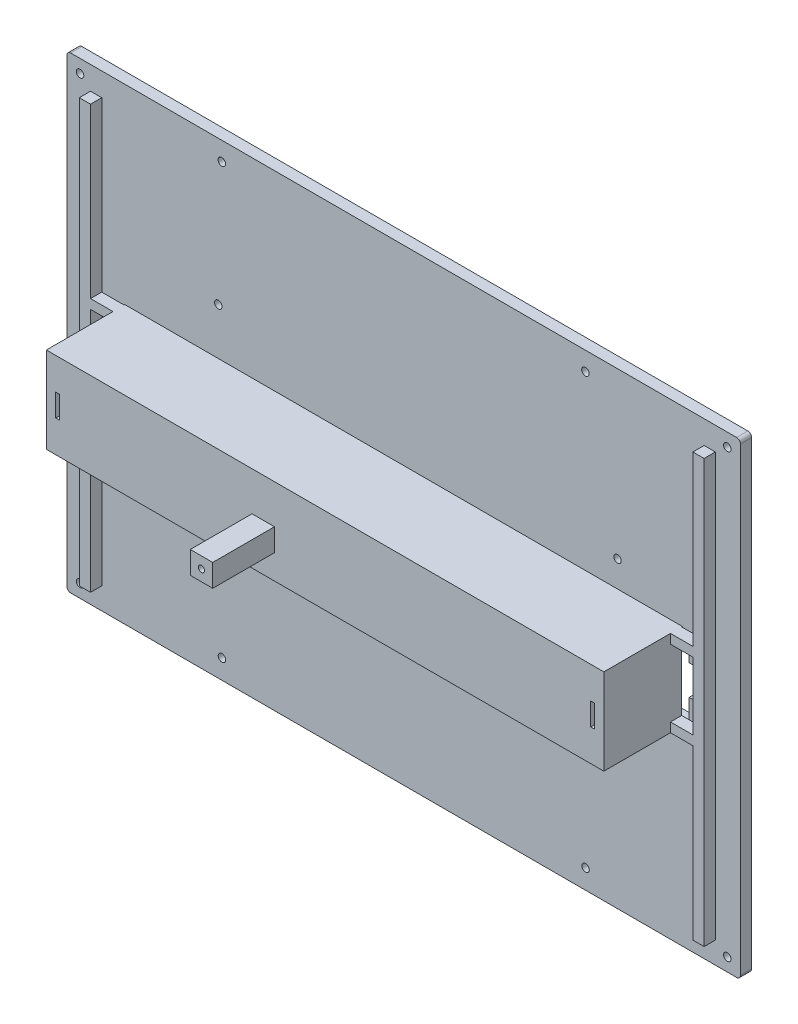
SolidWorks part; units mm, degrees
ref_plane "前视基准面" through (0, 0, 0) normal (0, 0, 1) x (1, 0, 0)
ref_plane "上视基准面" through (0, 0, 0) normal (0, 1, 0) x (1, 0, 0)
ref_plane "右视基准面" through (0, 0, 0) normal (1, 0, 0) x (0, 0, -1)
sketch "草图1" plane through (0, 0, 0) normal (0, 0, 1) x (1, 0, 0)
  line L1 (-90, 62.5) -> (90, 62.5)
  line L2 (-90, 62.5) -> (-90, -62.5)
  line L3 (-90, -62.5) -> (90, -62.5)
  line L4 (90, 62.5) -> (90, -62.5)
  line L5 (-90, 62.5) -> (90, -62.5) construction
  line L6 (-90, -62.5) -> (90, 62.5) construction
  point P0 (0, 0)
  dimension "D1" = 125
  dimension "D2" = 180
extrude "凸台-拉伸1" add sketch "草图1" along normal blind 3
sketch "草图7" plane through (0, 0, 0) normal (0, 0, -1) x (-1, 0, 0)
  line L1 (-72, 10.5) -> (72, 10.5)
  line L2 (-72, 10.5) -> (-72, -10.5)
  line L3 (-72, -10.5) -> (72, -10.5)
  line L4 (72, 10.5) -> (72, -10.5)
  line L5 (0, 0) -> (72.729, 0) construction
  line L8 (0, 0) -> (0, -50.9103) construction
  dimension "D1" = 21
  dimension "D2" = 144
extrude "电池位切除-拉伸3" cut sketch "草图7" against normal up to next
sketch "草图8" plane through (0, 0, 3) normal (0, 0, 1) x (1, 0, 0)
  line L0 (-72, 9.5) -> (72, 9.5)
  line L9 (-72, -9.5) -> (72, -9.5)
  line L10 (72, 0) -> (58.7112, 0) construction
  line L12 (72, 10.5) -> (72, -10.5) construction
  line L13 (-74.5, 11.5) -> (74.5, 11.5)
  line L14 (-74.5, 11.5) -> (-74.5, -11.5)
  line L15 (-74.5, -11.5) -> (74.5, -11.5)
  line L16 (74.5, 11.5) -> (74.5, -11.5)
  line L17 (-72, -10.5) -> (-72, 10.5) construction
  line L18 (-72, 10.5) -> (72, 10.5) construction
  line L19 (-72, 10.5) -> (72, 10.5) construction
  line L22 (72, 9.5) -> (72, -9.5)
  line L23 (-72, -10.5) -> (-72, 10.5) construction
  line L24 (-72, -9.5) -> (-72, 9.5)
  dimension "D1" = 2.5
  dimension "D2" = 2.5
  dimension "D3" = 2
  dimension "D4" = 2
extrude "凸台-拉伸2" add sketch "草图8" along normal blind 21
sketch "草图9" plane through (0, 0, 24) normal (0, 0, 1) x (1, 0, 0)
  line L0 (74.5, 11.5) -> (-74.5, 11.5) construction
  line L5 (74.5, 11.5) -> (-74.5, 11.5)
  line L6 (-74.5, -11.5) -> (74.5, -11.5) construction
  line L7 (-74.5, -11.5) -> (74.5, -11.5)
  line L8 (74.5, -11.5) -> (74.5, 11.5) construction
  line L9 (74.5, -11.5) -> (74.5, 11.5)
  line L10 (-74.5, 11.5) -> (-74.5, -11.5) construction
  line L11 (-74.5, 11.5) -> (-74.5, -11.5)
extrude "凸台-拉伸3" add sketch "草图9" against normal blind 2
sketch "草图4" plane through (0, 0, 0) normal (0, 0, -1) x (-1, 0, 0)
  line L0 (72, -10.5) -> (72, 10.5) construction
  line L5 (72, 0) -> (84.6307, 0) construction
  line L10 (83.2374, -53.4277) -> (79.3374, -53.4277) construction
  line L11 (83.2374, -49.6277) -> (83.2374, -53.4277) construction
  line L12 (79.3374, -49.6277) -> (83.2374, -49.6277) construction
  line L29 (72, -4) -> (74.5, -4)
  line L30 (74.5, -4) -> (74.5, 4)
  line L31 (74.5, 4) -> (72, 4)
  line L32 (72, 4) -> (72, -4)
  dimension "D1" = 8
  dimension "D2" = 2.5
extrude "切除-拉伸2" cut sketch "草图4" against normal blind 2 from offset 1.5 offset against normal yes
sketch "草图10" plane through (0, 0, 24) normal (0, 0, 1) x (1, 0, 0)
  line L0 (-16.5366, -1.9347) -> (8.5541, -1.9347) construction
  line L2 (-19.5366, 1.0653) -> (-19.5366, -4.9347)
  line L4 (-13.5366, 1.0653) -> (-13.5366, -4.9347)
  line L5 (-16.5366, -1.9347) -> (-16.5366, 4.0653) construction
  line L6 (0, 0) -> (60.8594, 0) construction
  line L7 (0, 0) -> (0, 60.5) construction
  line L8 (75, 60.5) -> (-75, 60.5) construction
  line L9 (-19.5366, 1.0653) -> (-13.5366, 1.0653)
  line L10 (-19.5366, -4.9347) -> (-13.5366, -4.9347)
  circle A0 centre (-16.5366, -1.9347) radius 0.825
  dimension "D2" = 1.65
  dimension "D1" = 6
extrude "凸台-拉伸4" add sketch "草图10" along normal up to surface (16.5 mm away)
sketch "草图11" plane through (0, 0, 0) normal (0, 0, -1) x (-1, 0, 0)
  circle A0 centre (-48.6147, -57.3) radius 1 construction
  circle A1 centre (-49.55, -23.8) radius 1 construction
  circle A2 centre (57.15, -18.3) radius 1 construction
  circle A3 centre (48.5747, -57.3) radius 1 construction
  circle A4 centre (86.5, 59) radius 1
  circle A5 centre (48.6147, 57.5) radius 1 construction
  circle A6 centre (-57.15, 18.5) radius 1 construction
  circle A7 centre (-48.5747, 57.5) radius 1 construction
  circle A8 centre (-48.6147, -57.3) radius 1
  circle A9 centre (-49.55, -23.8) radius 1
  circle A10 centre (57.15, -18.3) radius 1
  circle A11 centre (48.5747, -57.3) radius 1
  circle A13 centre (48.6147, 57.5) radius 1
  circle A14 centre (-57.15, 18.5) radius 1
  circle A15 centre (-48.5747, 57.5) radius 1
  circle A16 centre (49.55, 24) radius 1 construction
  circle A17 centre (49.55, 24) radius 1
  circle A18 centre (86.5, -59) radius 1
  circle A19 centre (-86.5, -59) radius 1
  circle A20 centre (-86.5, 59) radius 1
  dimension "D1" = 2
  dimension "D2" = 2
  dimension "D3" = 2
  dimension "D4" = 2
extrude "固定螺丝切除-拉伸3" cut sketch "草图11" against normal up to next
sketch "草图12" plane through (0, 0, 0) normal (0, 0, -1) x (-1, 0, 0)
  circle A0 centre (-48.5747, 57.5) radius 2
  circle A1 centre (-57.15, 18.5) radius 2
  circle A2 centre (-49.55, -23.8) radius 2
  circle A3 centre (-48.6147, -57.3) radius 2
  circle A4 centre (48.5747, -57.3) radius 2
  circle A5 centre (57.15, -18.3) radius 2
  circle A7 centre (-86.5, 59) radius 2
  circle A8 centre (48.6147, 57.5) radius 2
  circle A9 centre (49.55, 24) radius 2
  circle A10 centre (-86.5, -59) radius 2
  circle A11 centre (86.5, -59) radius 2
  circle A12 centre (86.5, 59) radius 2
  dimension "D1" = 4
  dimension "D2" = 4
  dimension "D3" = 4
  dimension "D4" = 4
  dimension "D5" = 4
extrude "固定螺丝凹陷切除-拉伸4" cut sketch "草图12" against normal blind 1.2
fillet "圆角1" radius 1 4 edges at (90, -62.5, 1.5) (-90, -62.5, 1.5) (-90, 62.5, 1.5) (90, 62.5, 1.5)
sketch "草图13" plane through (0, 0, 24) normal (0, 0, 1) x (1, 0, 0)
  line L0 (72, 10.5) -> (72, -10.5) construction
  line L1 (72, 3) -> (71, 3)
  line L2 (72, 3) -> (72, -3)
  line L3 (72, -3) -> (71, -3)
  line L4 (71, 3) -> (71, -3)
  line L5 (-72, -10.5) -> (-72, 10.5) construction
  line L6 (-71, 3) -> (-72, 3)
  line L7 (-71, 3) -> (-71, -3)
  line L8 (-71, -3) -> (-72, -3)
  line L9 (-72, 3) -> (-72, -3)
  line L10 (72, 0) -> (59.7453, 0) construction
  dimension "D1" = 1
  dimension "D2" = 6
  dimension "D3" = 1
  dimension "D4" = 6
extrude "切除-拉伸3" cut sketch "草图13" against normal up to next
sketch "草图14" plane through (0, 0, 22) normal (0, 0, -1) x (-1, 0, 0)
  line L0 (72, 10.5) -> (-72, 10.5) construction
  line L1 (-71, 10.5) -> (-69, 10.5)
  line L2 (-71, 10.5) -> (-71, 5.5)
  line L3 (-71, 5.5) -> (-69, 5.5)
  line L4 (-69, 10.5) -> (-69, 5.5)
  line L5 (-72, 0) -> (-60.8543, 0) construction
  line L6 (-72, 10.5) -> (-72, -10.5) construction
  line L7 (72, 0) -> (63.4917, 0) construction
  line L8 (69, 10.5) -> (71, 10.5)
  line L9 (69, 10.5) -> (69, 6)
  line L10 (69, 6) -> (71, 6)
  line L11 (71, 10.5) -> (71, 6)
  line L12 (72, -10.5) -> (72, 10.5) construction
  line L13 (71, -10.5) -> (71, -6)
  line L14 (69, -6) -> (71, -6)
  line L15 (69, -10.5) -> (69, -6)
  line L16 (69, -10.5) -> (71, -10.5)
  line L17 (-69, -10.5) -> (-69, -5.5)
  line L18 (-71, -5.5) -> (-69, -5.5)
  line L19 (-71, -10.5) -> (-71, -5.5)
  line L20 (-71, -10.5) -> (-69, -10.5)
  dimension "D1" = 1
  dimension "D2" = 2
  dimension "D3" = 4.5
  dimension "D4" = 1
  dimension "D5" = 2
  dimension "D6" = 5
extrude "凸台-拉伸5" add sketch "草图14" along normal blind 16
sketch "草图15" plane through (0, 0, 0) normal (0, 0, -1) x (-1, 0, 0)
  line L0 (72, 10.5) -> (-72, 10.5) construction
  line L5 (72, 10.5) -> (72, -10.5)
  line L7 (-72, -10.5) -> (72, -10.5) construction
  line L8 (-76.3, 10.5) -> (72, 10.5)
  line L9 (-76.3, 10.5) -> (-76.3, 4)
  line L10 (-76.3, -10.5) -> (72, -10.5)
  line L12 (-76.3, 4) -> (-79.3365, 4)
  line L14 (-76.3, -4) -> (-79.3365, -4)
  line L15 (-79.3365, 4) -> (-79.3365, -4)
  line L16 (72, 10.5) -> (-72, 10.5) construction
  line L17 (-76.3, -4) -> (-76.3, -10.5)
  line L18 (-76.1, -10.3) -> (-76.1, 10.3) construction
  line L19 (-79.2365, 3.5) -> (-79.2365, -3.5) construction
  dimension "D1" = 6.5
  dimension "D2" = 6.5
  dimension "D3" = 0.2
  dimension "D4" = 0.1
extrude "切除-拉伸6" cut sketch "草图15" against normal blind 3.2
sketch "草图17" plane through (0, 0, 0) normal (0, 0, -1) x (-1, 0, 0)
  line L0 (-76.3, 4) -> (-79.3365, 4) construction
  line L1 (-81.8365, 4) -> (-79.3365, 4)
  line L2 (-81.8365, 4) -> (-81.8365, -4)
  line L3 (-81.8365, -4) -> (-79.3365, -4)
  line L4 (-79.3365, 4) -> (-79.3365, -4)
  dimension "D1" = 2.5
extrude "切除-拉伸7" cut sketch "草图17" against normal blind 1.5
fillet "圆角2" radius 0.25 26 edges at (-71, 7.75, 6) (-70, 6, 6) (-69, 7.75, 6) (-69, -7.75, 6) (-70, -6, 6) (-71, -7.75, 6) (71, -7.5, 6) (70, -5.5, 6) (69, -7.5, 6) (69, 7.5, 6) (70, 5.5, 6) (71, 7.5, 6) (79.3365, 0, 3) (81.8365, 0, 0) (-69, 9.5, 14) (-71, 9.5, 14) (-71, -9.5, 14) (-69, -9.5, 14) (69, -9.5, 14) (71, -9.5, 14) (71, 9.5, 14) (69, 9.5, 14) (-70, 9.5, 6) (-70, -9.5, 6) (70, -9.5, 6) (70, 9.5, 6)
sketch "草图18" plane through (0, 0, 3) normal (0, 0, 1) x (1, 0, 0)
  line L0 (0, 0) -> (0, 49.5083) construction
  line L1 (-83.5, 56.5) -> (-80.5, 56.5)
  line L2 (-83.5, 56.5) -> (-83.5, -56.5)
  line L3 (-83.5, -56.5) -> (-80.5, -56.5)
  line L4 (-80.5, 56.5) -> (-80.5, 11.5)
  line L5 (89, 62.5) -> (-89, 62.5) construction
  line L6 (-89, -62.5) -> (89, -62.5) construction
  line L7 (-74.5, 11.5) -> (-74.5, -11.5) construction
  line L12 (-80.5, 9) -> (-80.5, -9)
  line L13 (-74.5, 11.5) -> (-80.5, 11.5)
  line L14 (-74.5, 11.5) -> (-74.5, 9)
  line L15 (-74.5, 9) -> (-80.5, 9)
  line L17 (-74.5, -11.5) -> (-80.5, -11.5)
  line L18 (-74.5, -11.5) -> (-74.5, -9)
  line L19 (-74.5, -9) -> (-80.5, -9)
  line L21 (-80.5, -11.5) -> (-80.5, -56.5)
  line L22 (80.5, -11.5) -> (80.5, -56.5)
  line L23 (74.5, -9) -> (80.5, -9)
  line L24 (74.5, -11.5) -> (74.5, -9)
  line L25 (74.5, -11.5) -> (80.5, -11.5)
  line L26 (74.5, 9) -> (80.5, 9)
  line L27 (74.5, 11.5) -> (74.5, 9)
  line L28 (74.5, 11.5) -> (80.5, 11.5)
  line L29 (80.5, 9) -> (80.5, -9)
  line L30 (80.5, 56.5) -> (80.5, 11.5)
  line L31 (83.5, -56.5) -> (80.5, -56.5)
  line L32 (83.5, 56.5) -> (83.5, -56.5)
  line L33 (83.5, 56.5) -> (80.5, 56.5)
  dimension "D1" = 6
  dimension "D2" = 6
  dimension "D3" = 3
  dimension "D4" = 6
  dimension "D5" = 2.5
extrude "凸台-拉伸6" add sketch "草图18" along normal blind 3 from surface starting at face at (0.625, 0, 3.2)
